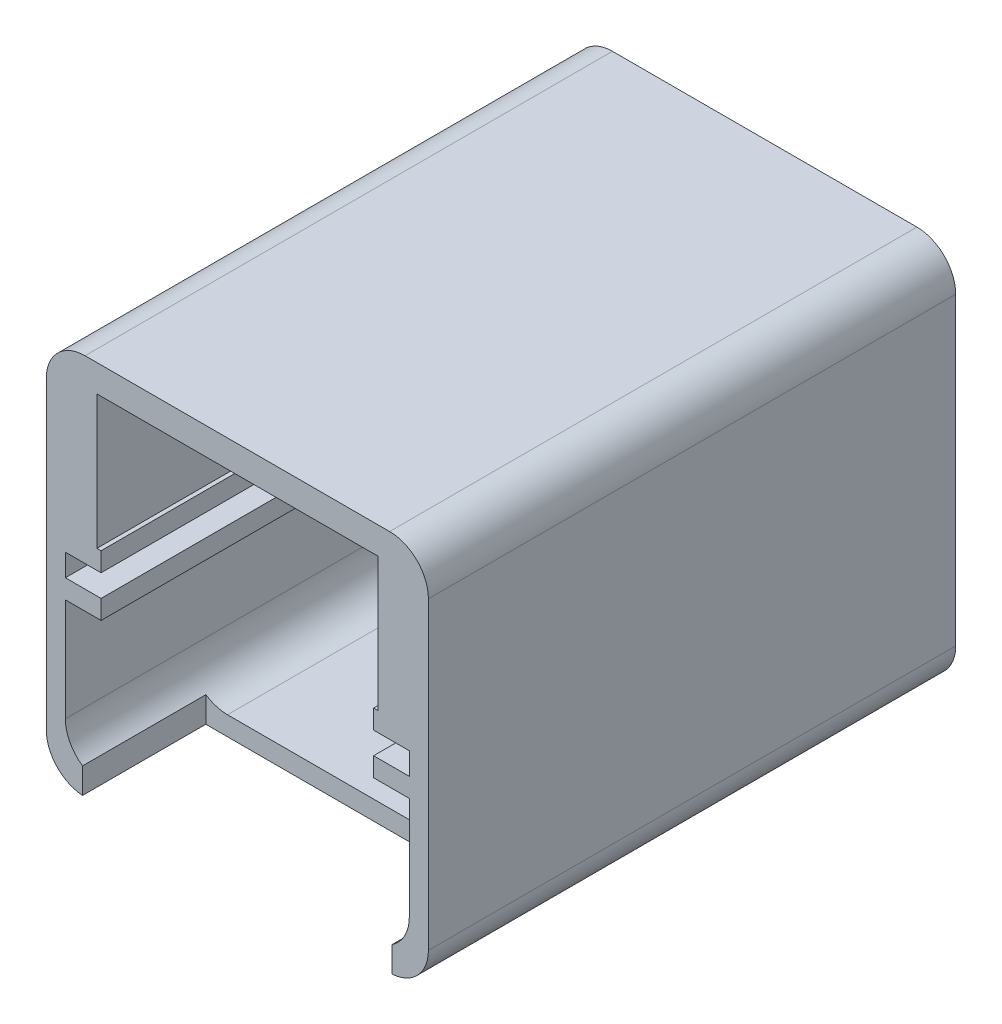
SolidWorks part; units mm, degrees
ref_plane "Front Plane" through (0, 0, 0) normal (0, 0, 1) x (1, 0, 0)
ref_plane "Top Plane" through (0, 0, 0) normal (0, 1, 0) x (1, 0, 0)
ref_plane "Right Plane" through (0, 0, 0) normal (1, 0, 0) x (0, 0, -1)
sketch "Sketch1" plane through (0, 0, 0) normal (0, 0, 1) x (1, 0, 0)
  line L1 (0, 0) -> (100, 0)
  line L2 (0, 0) -> (0, 100)
  line L3 (0, 100) -> (100, 100)
  line L4 (100, 0) -> (100, 100)
  line L5 (3, 3) -> (97, 3)
  line L6 (3, 3) -> (3, 97)
  line L7 (3, 97) -> (97, 97)
  line L8 (97, 3) -> (97, 97)
  dimension "D1" = 100
  dimension "D2" = 100
  dimension "D3" = 3
  dimension "D4" = 3
  dimension "D5" = 3
  dimension "D6" = 3
extrude "Boss-Extrude1" add sketch "Sketch1" along normal blind 250 contours L2 L1 L4 L3
sketch "Sketch2" plane through (0, 0, 0) normal (0, 0, -1) x (-1, 0, 0)
  line L1 (-95, 5) -> (-5, 5)
  line L2 (-95, 5) -> (-95, 95)
  line L3 (-95, 95) -> (-5, 95)
  line L4 (0, 100) -> (-100, 100)
  line L5 (-100, 100) -> (-100, 0)
  line L6 (-100, 0) -> (0, 0)
  line L7 (0, 0) -> (0, 100)
  line L8 (0, 100) -> (-100, 100)
  line L9 (-100, 100) -> (-100, 0)
  line L10 (-100, 0) -> (0, 0)
  line L11 (0, 0) -> (0, 100)
  line L12 (-5, 5) -> (-5, 95)
  dimension "D2" = 5
  dimension "D3" = 5
  dimension "D4" = 5
  dimension "D5" = 5
  dimension "D1" = 0
extrude "Cut-Extrude1" cut sketch "Sketch2" against normal through all contours L2 L1 L12 L3
fillet "Fillet1" radius 10.16 4 edges at (0, 100, 125) (0, 0, 125) (100, 100, 125) (100, 0, 125)
sketch "Sketch3" plane through (0, 0, 0) normal (0, 0, -1) x (-1, 0, 0)
  line L0 (-95, 50) -> (-5, 50) construction
  line L1 (-95, 5) -> (-95, 95) construction
  line L2 (-5, 5) -> (-5, 95) construction
  line L3 (-95, 57.9) -> (-85.6588, 57.9)
  line L4 (-85.6588, 57.9) -> (-85.6588, 52.9)
  line L5 (-85.6588, 52.9) -> (-95, 52.9)
  line L6 (-95, 52.9) -> (-95, 50)
  line L7 (-95, 50) -> (-95, 47.1)
  line L8 (-95, 47.1) -> (-85.6588, 47.1)
  line L9 (-85.6588, 47.1) -> (-85.6588, 42.1)
  line L10 (-85.6588, 42.1) -> (-95, 42.1)
  line L11 (-95, 42.1) -> (-95, 47.1)
  line L12 (-95, 57.9) -> (-95, 52.9)
  line L13 (-50, 67.1729) -> (-50, 35.9029) construction
  line L14 (-5, 42.1) -> (-5, 47.1)
  line L15 (-14.3412, 42.1) -> (-5, 42.1)
  line L16 (-14.3412, 47.1) -> (-14.3412, 42.1)
  line L17 (-5, 47.1) -> (-14.3412, 47.1)
  line L18 (-5, 57.9) -> (-5, 52.9)
  line L19 (-5, 57.9) -> (-14.3412, 57.9)
  line L20 (-14.3412, 57.9) -> (-14.3412, 52.9)
  line L21 (-14.3412, 52.9) -> (-5, 52.9)
  point P8 (-50, 50)
  dimension "D1" = 9.3412
  dimension "D2" = 5
  dimension "D3" = 5
  dimension "D4" = 5.8
  dimension "D5" = 2.9
extrude "Boss-Extrude2" add sketch "Sketch3" against normal through all contours L5 L4 L3 L12 | L8 L9 L10 L11 | L18 L21 L20 L19 | L14 L17 L16 L15
sketch "Sketch4" plane through (0, 100, 0) normal (0, 1, 0) x (1, 0, 0)
  line L0 (100, 0) -> (100, -250) construction
  line L1 (0, 0) -> (100, 0)
  line L2 (0, 0) -> (0, -125)
  line L3 (0, -125) -> (100, -125)
  line L4 (100, 0) -> (100, -125)
  dimension "D1" = 125
extrude "Cut-Extrude2" cut sketch "Sketch4" against normal through all
sketch "Sketch6" plane through (0, 5, 0) normal (0, 1, 0) x (1, 0, 0)
  line L0 (5, -250) -> (5, -125) construction
  line L1 (95, -125) -> (5, -125)
  line L2 (95, -125) -> (95, -130.08)
  line L3 (95, -130.08) -> (5, -130.08)
  line L4 (5, -125) -> (5, -130.08)
  dimension "D1" = 5.08
extrude "Boss-Extrude3" add sketch "Sketch6" along normal through all
sketch "Sketch7" plane through (0, 0, 125) normal (0, 0, -1) x (-1, 0, 0)
  line L0 (-50, 100) -> (-50, 0) construction
  line L1 (-5, 100) -> (-95, 100) construction
  line L2 (-10.16, 0) -> (-89.84, 0) construction
  line L3 (-100, 50) -> (0, 50) construction
  line L4 (-100, 10.16) -> (-100, 89.84) construction
  line L5 (0, 10.16) -> (0, 89.84) construction
  circle A0 centre (-50, 50) radius 45.3
  circle A1 centre (-50, 50) radius 48.3
  dimension "D1" = 96.6
  dimension "D2" = 90.6
extrude "Cut-Extrude4" cut sketch "Sketch7" against normal blind 5.08 contours A0
sketch "Sketch8" plane through (0, 0, 125) normal (0, 0, -1) x (-1, 0, 0)
  line L6 (-5, 100) -> (-95, 100)
  line L7 (-95, 100) -> (-95, 98.5921)
  line L8 (-100, 89.84) -> (-100, 10.16)
  line L9 (-89.84, 0) -> (-10.16, 0)
  line L10 (0, 10.16) -> (0, 89.84)
  line L11 (-5, 98.5921) -> (-5, 100)
  line L12 (-5, 100) -> (-95, 100)
  line L13 (-95, 100) -> (-95, 98.5921)
  line L14 (-100, 89.84) -> (-100, 10.16)
  line L15 (-89.84, 0) -> (-10.16, 0)
  line L16 (0, 10.16) -> (0, 89.84)
  line L17 (-5, 98.5921) -> (-5, 100)
  circle A0 centre (-50, 50) radius 45.3
  circle A1 centre (-50, 50) radius 45.3 construction
  arc A4 (-95, 98.5921) -> (-100, 89.84) centre (-89.84, 89.84) ccw
  arc A5 (-100, 10.16) -> (-89.84, 0) centre (-89.84, 10.16) ccw
  arc A6 (-10.16, 0) -> (0, 10.16) centre (-10.16, 10.16) ccw
  arc A7 (0, 89.84) -> (-5, 98.5921) centre (-10.16, 89.84) ccw
  arc A8 (-95, 98.5921) -> (-100, 89.84) centre (-89.84, 89.84) ccw
  arc A9 (-100, 10.16) -> (-89.84, 0) centre (-89.84, 10.16) ccw
  arc A10 (-10.16, 0) -> (0, 10.16) centre (-10.16, 10.16) ccw
  arc A11 (0, 89.84) -> (-5, 98.5921) centre (-10.16, 89.84) ccw
  dimension "D1" = 0
sketch "Sketch10" plane through (0, 0, 125) normal (0, 0, -1) x (-1, 0, 0)
  line L6 (-5, 100) -> (-95, 100)
  line L7 (-95, 100) -> (-95, 98.5921)
  line L8 (-100, 89.84) -> (-100, 10.16)
  line L9 (-89.84, 0) -> (-10.16, 0)
  line L10 (0, 10.16) -> (0, 89.84)
  line L11 (-5, 98.5921) -> (-5, 100)
  line L12 (-5, 100) -> (-95, 100)
  line L13 (-95, 100) -> (-95, 98.5921)
  line L14 (-100, 89.84) -> (-100, 10.16)
  line L15 (-89.84, 0) -> (-10.16, 0)
  line L16 (0, 10.16) -> (0, 89.84)
  line L17 (-5, 98.5921) -> (-5, 100)
  circle A0 centre (-50, 50) radius 48.3
  circle A1 centre (-50, 50) radius 45.3
  circle A2 centre (-50, 50) radius 45.3 construction
  arc A4 (-95, 98.5921) -> (-100, 89.84) centre (-89.84, 89.84) ccw
  arc A5 (-100, 10.16) -> (-89.84, 0) centre (-89.84, 10.16) ccw
  arc A6 (-10.16, 0) -> (0, 10.16) centre (-10.16, 10.16) ccw
  arc A7 (0, 89.84) -> (-5, 98.5921) centre (-10.16, 89.84) ccw
  arc A8 (-95, 98.5921) -> (-100, 89.84) centre (-89.84, 89.84) ccw
  arc A9 (-100, 10.16) -> (-89.84, 0) centre (-89.84, 10.16) ccw
  arc A10 (-10.16, 0) -> (0, 10.16) centre (-10.16, 10.16) ccw
  arc A11 (0, 89.84) -> (-5, 98.5921) centre (-10.16, 89.84) ccw
  dimension "D2" = 96.6
  dimension "D1" = 0
extrude "Boss-Extrude4" add sketch "Sketch10" along normal blind 30 contours A0
sketch "Sketch11" plane through (0, 0, 95) normal (0, 0, -1) x (-1, 0, 0)
  circle A1 centre (-50, 50) radius 45.3
  circle A2 centre (-50, 50) radius 45.3 construction
extrude "Cut-Extrude5" cut sketch "Sketch11" against normal up to surface (30 mm away) up to face at (98.3, 50, 125)
fillet "Fillet2" [suppressed] radius 2.54
sketch "Sketch13" plane through (0, 0, 0) normal (0, -1, 0) x (1, 0, 0)
  line L0 (10.16, 250) -> (89.84, 250) construction
  line L1 (81.75, 250) -> (18.25, 250)
  line L2 (81.75, 250) -> (81.75, 186.5)
  line L3 (81.75, 186.5) -> (18.25, 186.5)
  line L4 (18.25, 250) -> (18.25, 186.5)
  point P6 (50, 250)
  point P7 (50, 250)
  dimension "D1" = 63.5
  dimension "D2" = 63.5
extrude "Cut-Extrude7" cut sketch "Sketch13" against normal up to surface (5 mm away) up to face at (50, 5, 170.0533)
fillet "Fillet4" radius 1.27 3 edges at (18.25, 0, 218.25) (50, 0, 186.5) (81.75, 0, 218.25)
fillet "Fillet5" radius 10.16 4 edges at (95, 95, 190.04) (95, 5, 190.04) (5, 95, 190.04) (5, 5, 190.04)
sketch "Sketch14" plane through (0, 0, 125) normal (0, 0, -1) x (-1, 0, 0)
  line L0 (-50, 95.3) -> (-50, 50) construction
  line L6 (-5, 100) -> (-95, 100)
  line L7 (-95, 100) -> (-95, 98.5921)
  line L8 (-100, 89.84) -> (-100, 10.16)
  line L9 (-89.84, 0) -> (-10.16, 0)
  line L10 (0, 10.16) -> (0, 89.84)
  line L11 (-5, 98.5921) -> (-5, 100)
  line L12 (-5, 100) -> (-95, 100)
  line L13 (-95, 100) -> (-95, 98.5921)
  line L14 (-100, 89.84) -> (-100, 10.16)
  line L15 (-89.84, 0) -> (-10.16, 0)
  line L16 (0, 10.16) -> (0, 89.84)
  line L17 (-5, 98.5921) -> (-5, 100)
  circle A0 centre (-50, 50) radius 45.3 construction
  circle A1 centre (-50, 50) radius 48.3
  circle A2 centre (-50, 50) radius 48.3 construction
  arc A4 (-95, 98.5921) -> (-100, 89.84) centre (-89.84, 89.84) ccw
  arc A5 (-100, 10.16) -> (-89.84, 0) centre (-89.84, 10.16) ccw
  arc A6 (-10.16, 0) -> (0, 10.16) centre (-10.16, 10.16) ccw
  arc A7 (0, 89.84) -> (-5, 98.5921) centre (-10.16, 89.84) ccw
  arc A8 (-95, 98.5921) -> (-100, 89.84) centre (-89.84, 89.84) ccw
  arc A9 (-100, 10.16) -> (-89.84, 0) centre (-89.84, 10.16) ccw
  arc A10 (-10.16, 0) -> (0, 10.16) centre (-10.16, 10.16) ccw
  arc A11 (0, 89.84) -> (-5, 98.5921) centre (-10.16, 89.84) ccw
  dimension "D1" = 0
ref_plane "Plane1" through (14.3412, 52.9, 250) normal (0, 0, -1) x (-1, 0, 0)
extrude "Boss-Extrude6" add sketch "Sketch14" along direction (0, 0, 1) on the side of the normal up to surface (30 mm away) contours L12 L13 A8 L14 A9 L15 A10 L16 A11 L17 up to face at (4.7, 50, 95)
sketch "Sketch16" plane through (0, 0, 125) normal (0, 0, 1) x (1, 0, 0)
  circle A1 centre (50, 50) radius 45.3
  circle A2 centre (50, 50) radius 45.3
  dimension "D1" = 0
extrude "Cut-Extrude8" cut sketch "Sketch16" against normal through all
sketch "Sketch18" plane through (0, 0, 95) normal (0, 0, -1) x (-1, 0, 0)
  line L1 (-100, 89.84) -> (-100, 107.62)
  line L2 (-100, 107.62) -> (0, 107.62)
  line L3 (0, 107.62) -> (0, 89.84)
  line L4 (-5, 100) -> (-95, 100) construction
  line L5 (-89.84, 100) -> (-10.16, 100)
  arc A4 (-100, 89.84) -> (-89.84, 100) centre (-89.84, 89.84) cw
  arc A10 (-95, 98.5921) -> (-100, 89.84) centre (-89.84, 89.84) ccw construction
  arc A11 (0, 89.84) -> (-10.16, 100) centre (-10.16, 89.84) ccw
  arc A12 (0, 89.84) -> (-5, 98.5921) centre (-10.16, 89.84) ccw construction
  dimension "D1" = 7.62
extrude "Cut-Extrude10" cut sketch "Sketch18" against normal through all
sketch "Sketch19" plane through (0, 0, 0) normal (0, -1, 0) x (1, 0, 0)
  line L0 (83.02, 250) -> (89.84, 250) construction
  line L1 (90.5, 250) -> (9.5, 250)
  line L2 (90.5, 250) -> (90.5, 185.23)
  line L3 (90.5, 185.23) -> (9.5, 185.23)
  line L4 (9.5, 250) -> (9.5, 185.23)
  line L5 (84.84, 250) -> (15.16, 250) construction
  line L8 (83.02, 185.23) -> (16.98, 185.23) construction
  point P8 (50, 250)
  point P9 (50, 250)
  dimension "D1" = 81
extrude "Cut-Extrude11" cut sketch "Sketch19" against normal blind 25.4
sketch "Sketch20" plane through (0, 0, 0) normal (0, -1, 0) x (1, 0, 0)
  line L0 (9.5, 250) -> (9.5, 185.23) construction
  line L1 (9.5, 217.73) -> (90.5, 217.73)
  line L2 (9.5, 217.73) -> (9.5, 185.23)
  line L3 (9.5, 185.23) -> (90.5, 185.23)
  line L4 (90.5, 217.73) -> (90.5, 185.23)
  line L5 (90.5, 185.23) -> (90.5, 250) construction
  line L6 (89.84, 185.23) -> (10.16, 185.23) construction
  dimension "D1" = 32.5
extrude "Boss-Extrude7" add sketch "Sketch20" against normal up to surface (5 mm away) contours L2 L1 L4 L3 up to face at (50, 5, 148.4633)
sketch "Sketch21" plane through (0, 0, 185.23) normal (0, 0, 1) x (1, 0, 0)
  line L0 (15.16, 5) -> (15.16, 0)
  line L1 (15.16, 0) -> (9.5, 0)
  line L2 (84.84, 5) -> (90.5, 5)
  line L3 (90.5, 5) -> (90.5, 6.7226)
  line L4 (84.84, 5) -> (90.5, 5)
  line L5 (90.5, 5) -> (90.5, 6.7226)
  line L6 (9.5, 5) -> (15.16, 5)
  line L7 (9.5, 6.7226) -> (9.5, 5)
  line L8 (9.5, 5) -> (15.16, 5)
  line L9 (9.5, 6.7226) -> (9.5, 5)
  line L10 (84.84, 5) -> (84.84, 0)
  line L11 (84.84, 0) -> (90.5, 0)
  line L14 (90.5, 0.0215) -> (90.5, 5)
  line L15 (90.5, 5) -> (9.5, 5)
  line L16 (9.5, 5) -> (9.5, 0.0215)
  line L17 (9.5, 0.0215) -> (9.5, 0)
  line L18 (9.5, 0) -> (90.5, 0)
  line L19 (90.5, 0) -> (90.5, 0.0215)
  line L20 (90.5, 0.0215) -> (90.5, 5)
  line L21 (90.5, 5) -> (9.5, 5)
  line L22 (9.5, 5) -> (9.5, 0.0215)
  line L23 (9.5, 0.0215) -> (9.5, 0)
  line L24 (9.5, 0) -> (90.5, 0)
  line L25 (90.5, 0) -> (90.5, 0.0215)
  arc A1 (84.84, 5) -> (90.5, 6.7226) centre (84.84, 15.16) ccw
  arc A2 (84.84, 5) -> (90.5, 6.7226) centre (84.84, 15.16) ccw
  arc A3 (9.5, 6.7226) -> (15.16, 5) centre (15.16, 15.16) ccw
  arc A4 (9.5, 6.7226) -> (15.16, 5) centre (15.16, 15.16) ccw
  line M13 (84.84, 5) -> (90.5, 5)
  line M14 (90.5, 5) -> (90.5, 6.7226)
  arc M15 (90.5, 6.7226) -> (84.84, 5) centre (84.84, 15.16) cw
  dimension "D1" = 0
  dimension "D2" = 0
  dimension "D3" = 0
extrude "Boss-Extrude8" add sketch "Sketch21" along normal up to surface (32.5 mm away) contours M15 M13 M14 | A4 L8 L9 region at (89.1101, 5.5083, 185.23) up to face at (50, 1.6738, 217.73)
sketch "Sketch24" plane through (0, 0, 130.08) normal (0, 0, 1) x (1, 0, 0)
  line L0 (5, 57.9) -> (5, 84.84) construction
  line L1 (95, 57.9) -> (86.75, 57.9)
  line L2 (95, 57.9) -> (95, 95)
  line L3 (95, 95) -> (5, 95)
  line L4 (5, 57.9) -> (5, 95)
  line L5 (84.84, 95) -> (15.16, 95) construction
  line L6 (10.16, 100) -> (89.84, 100) construction
  line L8 (86.75, 57.9) -> (86.75, 92.9)
  line L9 (86.75, 92.9) -> (13.25, 92.9)
  line L10 (13.25, 57.9) -> (13.25, 92.9)
  line L11 (13.25, 57.9) -> (5, 57.9)
  point P15 (50, 100)
  point P16 (50, 92.9)
  dimension "D1" = 73.5
  dimension "D2" = 35
extrude "Boss-Extrude10" add sketch "Sketch24" along normal up to surface (119.92 mm away) contours L1 L8 L9 L10 L11 L4 L3 L2 up to face at (50, 50.2195, 250)
sketch "Sketch25" plane through (0, 0, 130.08) normal (0, 0, 1) x (1, 0, 0)
  line L1 (13.25, 92.9) -> (86.75, 92.9)
  line L2 (13.25, 92.9) -> (13.25, 76.4864)
  line L3 (13.25, 76.4864) -> (86.75, 76.4864)
  line L4 (86.75, 92.9) -> (86.75, 76.4864)
extrude "Boss-Extrude11" add sketch "Sketch25" along normal blind 6.35 contours L2 L1 L4 L3
sketch "Sketch26" plane through (100, 0, 0) normal (1, 0, 0) x (0, 0, -1)
  line L0 (-95, 89.84) -> (-95, 10.16) construction
  line L1 (-112, 112.7565) -> (-95, 112.7565)
  line L2 (-112, 112.7565) -> (-112, -12.4276)
  line L3 (-112, -12.4276) -> (-95, -12.4276)
  line L4 (-95, 112.7565) -> (-95, -12.4276)
  dimension "D1" = 17
extrude "Cut-Extrude12" cut sketch "Sketch26" against normal through all
